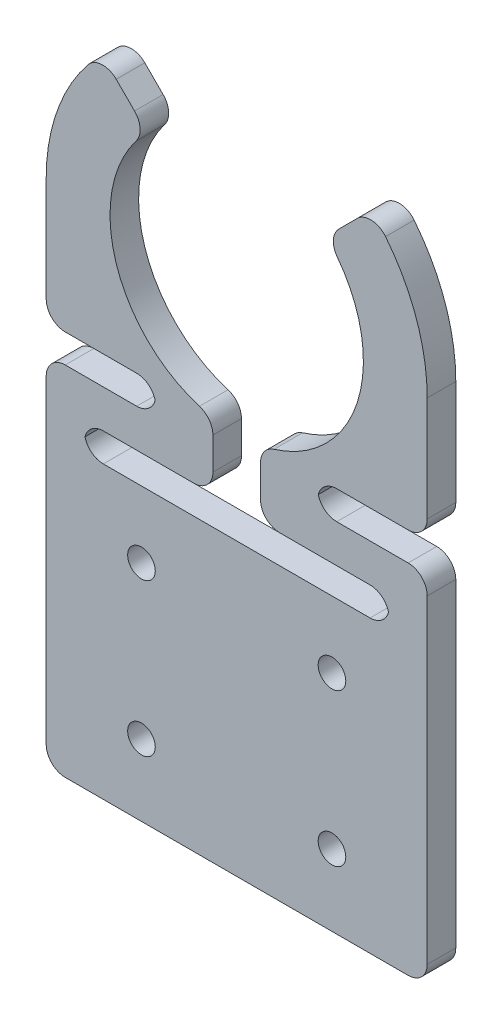
SolidWorks part; units mm, degrees
material "A-玻璃纤维"
ref_plane "前视基准面" through (0, 0, 0) normal (0, 0, 1) x (1, 0, 0)
ref_plane "上视基准面" through (0, 0, 0) normal (0, 1, 0) x (1, 0, 0)
ref_plane "右视基准面" through (0, 0, 0) normal (1, 0, 0) x (0, 0, -1)
sketch "草图1" plane through (0, 0, 0) normal (0, 0, 1) x (1, 0, 0)
  line L0 (10, 0) -> (-10, 0) construction
  line L1 (0, 0) -> (0, 30) construction
  line L2 (0, 30) -> (-14.1421, 44.1421) construction
  line L3 (0, 30) -> (14.1421, 44.1421) construction
  line L4 (-9.4045, 39.4045) -> (-14.1421, 44.1421)
  line L5 (14.1421, 44.1421) -> (9.4045, 39.4045)
  line L6 (-20, 30) -> (-20, -23.5)
  line L7 (-20, -23.5) -> (20, -23.5)
  line L8 (20, -23.5) -> (20, 30)
  line L9 (10, -16) -> (-10, -16) construction
  circle A0 centre (-10, 0) radius 1.45
  circle A1 centre (10, 0) radius 1.45
  arc A2 (-9.4045, 39.4045) -> (9.4045, 39.4045) centre (0, 30) ccw
  arc A3 (-14.1421, 44.1421) -> (-20, 30) centre (0, 30) ccw
  arc A4 (20, 30) -> (14.1421, 44.1421) centre (0, 30) ccw
  circle A5 centre (-10, -16) radius 1.45
  circle A6 centre (10, -16) radius 1.45
  point P4 (0, 0)
  point P19 (0, -16)
  point P21 (0, 0)
  dimension "D2" = 2.9
  dimension "D4" = 26.6
  dimension "D7" = 20
  dimension "D8" = 16
  dimension "D1" = 20
  dimension "D3" = 30
  dimension "D5" = 90
  dimension "D6" = 135
  dimension "D9" = 7.5
  dimension "D10" = 20
extrude "凸台-拉伸1" add sketch "草图1" along normal blind 3
sketch "草图2" plane through (0, 0, 3) normal (0, 0, 1) x (1, 0, 0)
  line L1 (-2.5, 7) -> (2.5, 7)
  line L2 (-2.5, 7) -> (-2.5, 32)
  line L3 (-2.5, 32) -> (2.5, 32)
  line L4 (2.5, 7) -> (2.5, 32)
  line L5 (-2.5, 7) -> (2.5, 32) construction
  line L6 (-2.5, 32) -> (2.5, 7) construction
  point P0 (0, 19.5)
  dimension "D1" = 7
  dimension "D2" = 5
  dimension "D3" = 25
extrude "切除-拉伸1" cut sketch "草图2" against normal through all
sketch "草图3" plane through (0, 0, 3) normal (0, 0, 1) x (1, 0, 0)
  line L0 (-20, 30) -> (-20, -23.5) construction
  line L1 (-20, 17) -> (-8.5, 17)
  line L2 (-20, 17) -> (-20, 14)
  line L3 (-20, 14) -> (-8.5, 14)
  line L4 (-8.5, 17) -> (-8.5, 14)
  line L5 (-2.5, 16.9371) -> (-2.5, 7) construction
  line L6 (-2.5, 7) -> (-16, 7)
  line L7 (-2.5, 7) -> (-2.5, 10)
  line L8 (-2.5, 10) -> (-16, 10)
  line L9 (-16, 7) -> (-16, 10)
  line L10 (0, -1000) -> (0, 49000) construction
  line L11 (16, 7) -> (16, 10)
  line L12 (2.5, 10) -> (16, 10)
  line L13 (2.5, 7) -> (2.5, 10)
  line L14 (2.5, 7) -> (16, 7)
  line L15 (8.5, 17) -> (8.5, 14)
  line L16 (20, 14) -> (8.5, 14)
  line L17 (20, 17) -> (20, 14)
  line L18 (20, 17) -> (8.5, 17)
  dimension "D1" = 3
  dimension "D2" = 4
  dimension "D3" = 3
  dimension "D4" = 6
  dimension "D5" = 4
extrude "切除-拉伸2" cut sketch "草图3" against normal through all
fillet "圆角1" radius 2 22 edges at (8.5, 17, 1.5) (8.5, 14, 1.5) (20, 14, 1.5) (20, -23.5, 1.5) (-20, -23.5, 1.5) (-20, 14, 1.5) (-8.5, 14, 1.5) (-8.5, 17, 1.5) (-20, 17, 1.5) (-14.1421, 44.1421, 1.5) (-2.5, 16.9371, 1.5) (-2.5, 10, 1.5) (-16, 10, 1.5) (-16, 7, 1.5) (16, 7, 1.5) (16, 10, 1.5) (2.5, 10, 1.5) (2.5, 16.9371, 1.5) (9.4045, 39.4045, 1.5) (14.1421, 44.1421, 1.5) (20, 17, 1.5) (-9.4045, 39.4045, 1.5)
